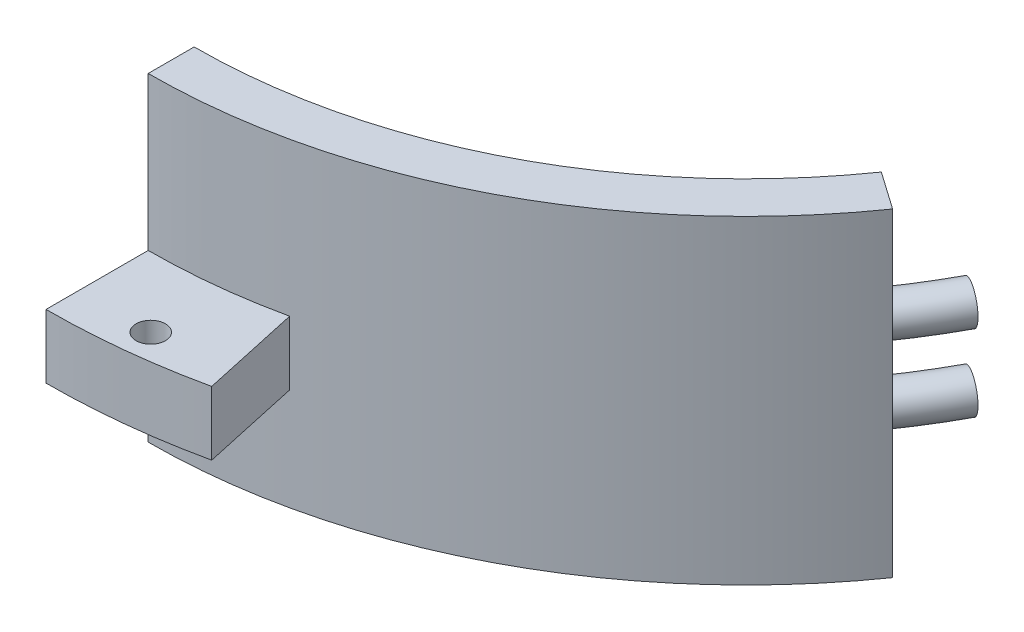
SolidWorks part; units mm, degrees
ref_plane "Front Plane" through (0, 0, 0) normal (0, 0, 1) x (1, 0, 0)
ref_plane "Top Plane" through (0, 0, 0) normal (0, 1, 0) x (1, 0, 0)
ref_plane "Right Plane" through (0, 0, 0) normal (1, 0, 0) x (0, 0, -1)
sketch "Sketch2" plane through (0, 0, 0) normal (0, 1, 0) x (1, 0, 0)
  line L0 (0, -46.8) -> (0, -43.2)
  line L1 (38.3363, -26.8434) -> (35.3874, -24.7785)
  line L2 (0, 0) -> (35.3874, -24.7785) construction
  circle A0 centre (0, 0) radius 46.8
  circle A1 centre (0, 0) radius 43.2
  dimension "D1" = 93.6
  dimension "D3" = 55
  dimension "D2" = 3.6
extrude "Boss-Extrude1" add sketch "Sketch2" along normal blind 25 contours A1 L0 A0 L1 region at (20.0007, 0, 38.421)
sketch "Sketch3" plane through (0, 25, 0) normal (0, 1, 0) x (1, 0, 0)
  line L0 (0, -43.2) -> (0, -40)
  line L1 (35.3874, -24.7785) -> (32.7661, -22.9431)
  line L2 (38.3363, -26.8434) -> (35.3874, -24.7785) construction
  circle A0 centre (0, 0) radius 40
  circle A2 centre (0, 0) radius 44.8
  arc M6 (35.3874, -24.7785) -> (0, -43.2) centre (0, 0) cw
  dimension "D1" = 80
  dimension "D2" = 89.6
extrude "Boss-Extrude2" add sketch "Sketch3" against normal blind 13 from offset 6 contours A0 L0 L1 M6 region at (18.4888, 25, 35.5166) offset against normal yes
sketch "Sketch4" plane through (0, 25, 0) normal (0, 1, 0) x (1, 0, 0)
  line L0 (0, -46.8) -> (0, -54.8)
  line L1 (10, -45.7191) -> (11.7094, -53.5344)
  line L2 (0, 0) -> (10, -45.7191) construction
  circle A0 centre (0, 0) radius 54.8
  arc A2 (0, -46.8) -> (38.3363, -26.8434) centre (0, 0) ccw construction
  circle A3 centre (0, 0) radius 46.8
  arc M7 (0, -46.8) -> (38.3363, -26.8434) centre (0, 0) ccw
  dimension "D1" = 8
  dimension "D2" = 10
extrude "Boss-Extrude3" add sketch "Sketch4" against normal blind 5 from offset 12 contours L0 A0 L1 M7 region at (5.4597, 25, 50.5125) offset against normal yes
sketch "Sketch5" plane through (0, 13, 0) normal (0, 1, 0) x (1, 0, 0)
  line L0 (5.0291, -46.529) -> (5.8888, -54.4827) construction
  circle A0 centre (5.647, -52.2457) radius 1.15
  arc A1 (0, -46.8) -> (10, -45.7191) centre (0, 0) ccw construction
  arc A2 (0, -54.8) -> (11.7094, -53.5344) centre (0, 0) ccw construction
  dimension "D1" = 2.3
  dimension "D2" = 2.25
extrude "M2 holes" cut sketch "Sketch5" against normal up to next
sketch "Sketch6" plane through (0, 19, 0) normal (0, 1, 0) x (1, 0, 0)
  line L0 (0, -40) -> (0, -43)
  line L1 (0, -43.2) -> (0, -40) construction
  line L2 (0, -43) -> (5, -39.6863)
  arc A0 (0, -40) -> (32.7661, -22.9431) centre (0, 0) ccw construction
  arc A1 (0, -40) -> (5, -39.6863) centre (0, 0) ccw
  dimension "D1" = 3
  dimension "D2" = 5
extrude "Cut-Extrude1" cut sketch "Sketch6" against normal up to next
sketch "Sketch7" plane through (0, 0, 0) normal (0.5736, 0, -0.8192) x (-0.8192, 0, -0.5736)
  line L1 (-40, 6) -> (-40, 19) construction
  line L2 (-24.7785, 19) -> (-43.2, 19) construction
  line L3 (-43.2, 6) -> (-40, 6) construction
  circle A0 centre (-43.4, 15.5) radius 1.5
  circle A1 centre (-43.4, 9.5) radius 1.5
  dimension "D1" = 3
  dimension "D2" = 3.4
  dimension "D3" = 3.5
  dimension "D4" = 3.5
sketch "Sketch9" plane through (0, 25, 0) normal (0, 1, 0) x (1, 0, 0)
  line L0 (0, 0) -> (35.3874, -24.7785) construction
  line L1 (0, 0) -> (38.0134, -20.5236) construction
  arc A0 (35.3874, -24.7785) -> (38.0134, -20.5236) centre (0, 0) ccw
  arc A1 (0, -43.2) -> (35.3874, -24.7785) centre (0, 0) ccw construction
  dimension "D1" = 5
sweep "Sweep1" add profiles "Sketch7" path "Sketch9"
